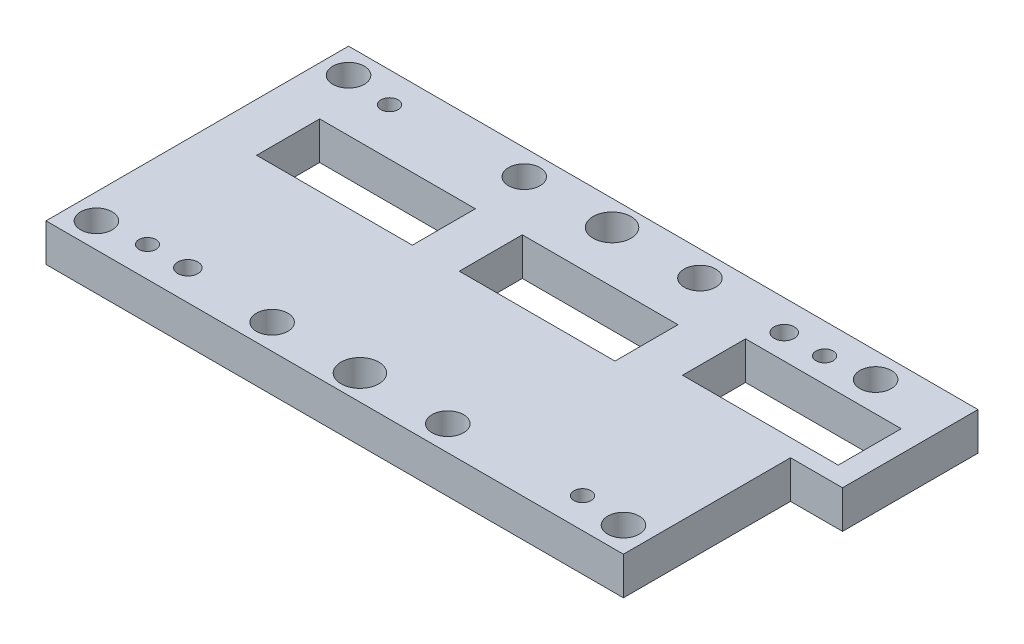
SolidWorks part; units mm, degrees
material "Plain Carbon Steel"
ref_plane "Front Plane" through (0, 0, 0) normal (0, 0, 1) x (1, 0, 0)
ref_plane "Top Plane" through (0, 0, 0) normal (0, 1, 0) x (1, 0, 0)
ref_plane "Right Plane" through (0, 0, 0) normal (1, 0, 0) x (0, 0, -1)
sketch "Sketch1" plane through (0, 0, 0) normal (0, 1, 0) x (1, 0, 0)
  line L0 (-229, 15.28) -> (-229, 9.28) construction
  line L1 (-229, -60) -> (0, -60)
  line L2 (-229, -60) -> (-229, 60)
  line L3 (-229, 60) -> (0, 60)
  line L4 (0, -60) -> (0, 60)
  point P0 (0, 0)
  dimension "D1" = 120
  dimension "D2" = 229
extrude "Boss-Extrude1" add sketch "Sketch1" against normal blind 15
sketch "Sketch2" plane through (0, 0, 0) normal (0, 1, 0) x (1, 0, 0)
  line L0 (21.6325, 5.27) -> (21.6325, 60) construction
  line L1 (0, 60) -> (20.6325, 60)
  line L2 (0, 60) -> (0, 6.27)
  line L3 (0, 6.27) -> (20.6325, 6.27)
  line L4 (20.6325, 60) -> (20.6325, 6.27)
  line L5 (1, 5.27) -> (21.6325, 5.27) construction
  dimension "D1" = 1
  dimension "D2" = 1
extrude "Boss-Extrude2" add sketch "Sketch2" against normal up to surface (15 mm away) up to face at (-114.5, -15, 0)
sketch "Sketch3" plane through (0, 0, 0) normal (0, 1, 0) x (1, 0, 0)
  line L0 (-48.75, 9.28) -> (-48.75, 26.191) construction
  line L1 (-49.75, 13.191) -> (12, 13.191)
  line L2 (-49.75, 13.191) -> (-49.75, 38.191)
  line L3 (-49.75, 38.191) -> (12, 38.191)
  line L4 (12, 13.191) -> (12, 38.191)
  line L5 (11, 27.5) -> (11, 9.28) construction
  line L7 (-29.25, 28.191) -> (-48.75, 28.191) construction
  dimension "D1" = 1
  dimension "D2" = 1
  dimension "D3" = 25
  dimension "D4" = 10
extrude "Cut-Extrude1" cut sketch "Sketch3" against normal up to next
sketch "Sketch4" plane through (0, 0, 0) normal (0, 1, 0) x (1, 0, 0)
  line L0 (-69, 15.28) -> (-69, 9.28) construction
  line L1 (-129.75, 29.6524) -> (-68, 29.6524)
  line L2 (-129.75, 29.6524) -> (-129.75, 4.6524)
  line L3 (-129.75, 4.6524) -> (-68, 4.6524)
  line L4 (-68, 29.6524) -> (-68, 4.6524)
  line L5 (-128.75, 9.28) -> (-128.75, 15.28) construction
  line L6 (-109.25, 19.6524) -> (-128.75, 19.6524) construction
  dimension "D1" = 1
  dimension "D2" = 1
  dimension "D3" = 10
  dimension "D4" = 25
extrude "Cut-Extrude2" cut sketch "Sketch4" against normal up to next
sketch "Sketch5" plane through (0, 0, 0) normal (0, 1, 0) x (1, 0, 0)
  line L0 (-208.75, 9.28) -> (-208.75, 15.28) construction
  line L1 (-209.75, 29.28) -> (-148, 29.28)
  line L2 (-209.75, 29.28) -> (-209.75, 4.28)
  line L3 (-209.75, 4.28) -> (-148, 4.28)
  line L4 (-148, 29.28) -> (-148, 4.28)
  line L5 (-149, 15.28) -> (-149, 9.28) construction
  line L6 (-149, 19.28) -> (-168.75, 19.28) construction
  dimension "D1" = 1
  dimension "D2" = 1
  dimension "D3" = 10
  dimension "D4" = 25
extrude "Cut-Extrude3" cut sketch "Sketch5" against normal up to next
sketch "Sketch7" plane through (0, 0, 0) normal (0, 1, 0) x (1, 0, 0)
  circle A0 centre (-114.5, 50) radius 7.5 construction
  circle A1 centre (-114.5, -50) radius 7.5 construction
  circle A2 centre (-114.5, 50) radius 7.5
  circle A3 centre (-114.5, -50) radius 7.5
extrude "Cut-Extrude5" cut sketch "Sketch7" against normal up to next
sketch "Sketch14" plane through (0, 0, 0) normal (0, 1, 0) x (1, 0, 0)
  circle A0 centre (-219, -50) radius 6.25 construction
  circle A1 centre (-149.323, -50) radius 6.25 construction
  circle A2 centre (-79.646, -50) radius 6.25 construction
  circle A3 centre (-219, 50) radius 6.25 construction
  circle A7 centre (-219, 50) radius 6.25
  circle A8 centre (-9.969, -50) radius 6.25 construction
  circle A9 centre (-9.969, 50) radius 6.25 construction
  circle A10 centre (-79.646, 50) radius 6.25 construction
  circle A11 centre (-149.323, 50) radius 6.25 construction
  circle A12 centre (-219, -50) radius 6.25
  circle A13 centre (-149.323, -50) radius 6.25
  circle A14 centre (-79.646, -50) radius 6.25
  circle A15 centre (-9.969, -50) radius 6.25
  circle A16 centre (-9.969, 50) radius 6.25
  circle A17 centre (-79.646, 50) radius 6.25
  circle A18 centre (-149.323, 50) radius 6.25
extrude "Cut-Extrude7" cut sketch "Sketch14" against normal up to next
hole_wizard "M8 Tapped Hole1" positions "Sketch17" profile "Sketch16" tap size "M8" standard "ISO" end condition through all
sketch "Sketch17" plane through (0, 0, 0) normal (0, 1, 0) x (1, 0, 0)
  line L0 (20.6325, 60) -> (-229, 60) construction
  line L1 (-229, -60) -> (0, -60) construction
  circle A0 centre (-219, 50) radius 6.25 construction
  circle A1 centre (-9.969, 50) radius 6.25 construction
  point P0 (-200.75, -48)
  point P2 (-28.219, -48)
  point P4 (-28.219, 48)
  point P6 (-200.75, 48)
  dimension "D2" = 12
  dimension "D3" = 12
  dimension "D1" = 12
  dimension "D4" = 12
sketch "Sketch16" plane through (-200.75, 0, 48) normal (1, 0, 0) x (0, 0, 1)
  line L0 (0, 0) -> (0, 15)
  line L1 (0, 15) -> (3.4, 15)
  line L2 (3.4, 15) -> (3.4, 0)
  line L5 (3.4, 0) -> (0, 0)
  line L11 (0, -6.35) -> (0, 107.95) construction
  dimension "Thru Tap Drill Dia." = 6.8
  dimension "Thru Tap Drill Depth" = 15
cosmetic thread "Hole Thread1"
cosmetic thread "Hole Thread2"
cosmetic thread "Hole Thread3"
cosmetic thread "Hole Thread4"
hole_wizard "Ø8.0mm Dowel Hole1" positions "Sketch20" profile "Sketch19" hole size "Ø8.0" standard "ISO" end condition through all
sketch "Sketch20" plane through (0, 0, 0) normal (0, 1, 0) x (1, 0, 0)
  line L0 (20.6325, 60) -> (-229, 60) construction
  line L1 (-229, -60) -> (0, -60) construction
  circle A0 centre (-28.219, 48) radius 3.4 construction
  circle A1 centre (-200.75, -48) radius 3.4 construction
  point P0 (-184.75, -48)
  point P2 (-44.219, 48)
  dimension "D2" = 16
  dimension "D4" = 16
  dimension "D1" = 12
  dimension "D3" = 12
sketch "Sketch19" plane through (-184.75, 0, 48) normal (1, 0, 0) x (0, 0, 1)
  line L0 (0, 0) -> (0, 15)
  line L1 (0, 15) -> (4, 15)
  line L2 (4, 15) -> (4, 0)
  line L5 (4, 0) -> (0, 0)
  line L11 (0, -6.35) -> (0, 107.95) construction
  dimension "Thru Hole Dia." = 8
  dimension "Thru Hole Depth" = 15
